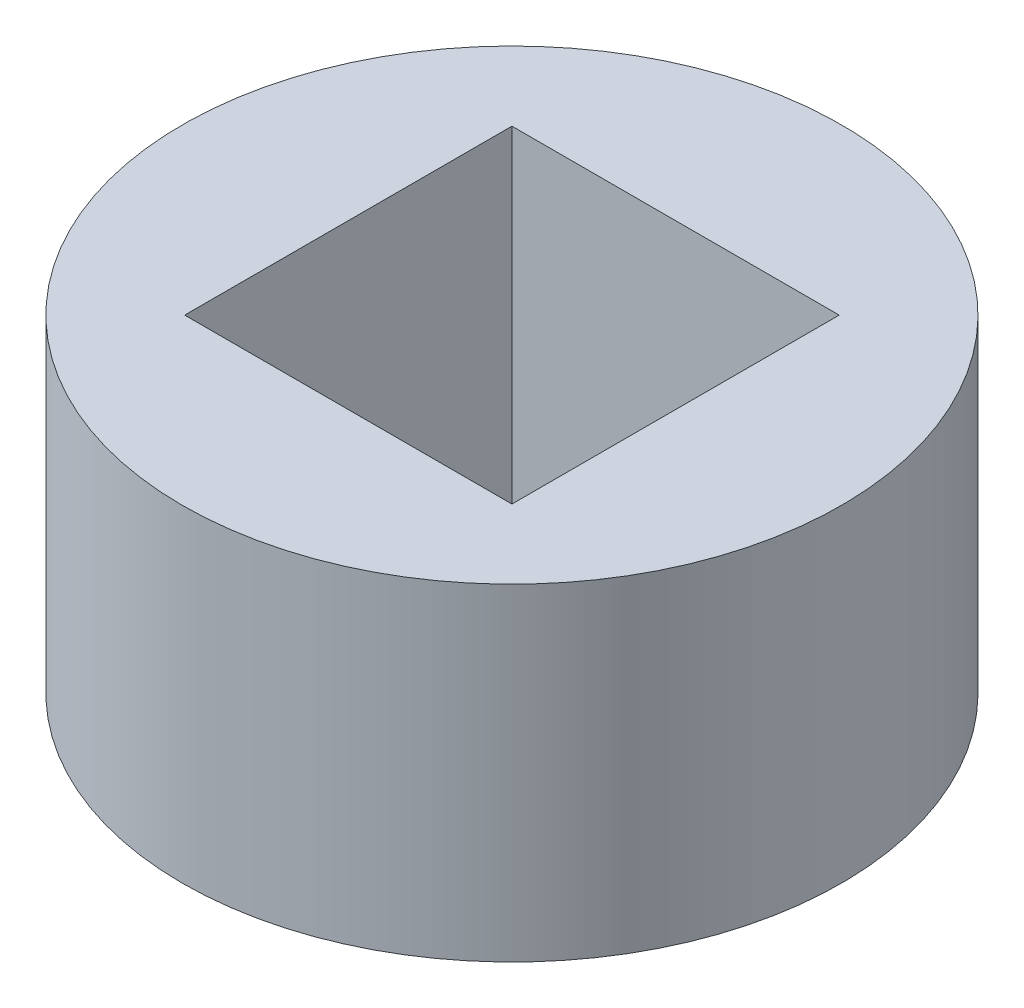
SolidWorks part; units mm, degrees
ref_plane "Front Plane" through (0, 0, 0) normal (0, 0, 1) x (1, 0, 0)
ref_plane "Top Plane" through (0, 0, 0) normal (0, 1, 0) x (1, 0, 0)
ref_plane "Right Plane" through (0, 0, 0) normal (1, 0, 0) x (0, 0, -1)
sketch "Elevator Axle Bearing" plane through (0, 0, 0) normal (0, 1, 0) x (1, 0, 0)
  line L1 (-3.175, 3.175) -> (3.175, 3.175)
  line L2 (-3.175, 3.175) -> (-3.175, -3.175)
  line L3 (-3.175, -3.175) -> (3.175, -3.175)
  line L4 (3.175, 3.175) -> (3.175, -3.175)
  line L5 (-3.175, 3.175) -> (3.175, -3.175) construction
  line L6 (-3.175, -3.175) -> (3.175, 3.175) construction
  circle A0 centre (0, 0) radius 6.3951
  dimension "D1" = 12.7903
  dimension "D2" = 6.35
  dimension "D3" = 6.35
extrude "Boss-Extrude1" add sketch "Elevator Axle Bearing" along normal blind 6.35
equation "\"Ball Diameter\"= 1.75in"
equation "\"Sheet Thickness\"= 0.25in"
equation "\"Screw Diameter\"= .17in"
equation "\"Robot Diameter\"= 14in"
equation "\"Castor Screw Diameter\"= 0.22in"
equation "\"Wheel Diameter\" = 4in"
equation "\"Nut Diameter\" = 8.4mm"
equation "\"Nut Height\" = 2.9mm"
equation "\"Screw Height\" = 0.55in"
equation "\"Pulley Diameter\" = 1in"
equation "\"Reactor Height\" = 14in"
equation "\"Elevator Height\" = 11.5in"
equation "\"Elevator Width\" = \"Ball Diameter\" + 0.25in"
equation "\"Elevator Bearing Diameter\" = sqr(2*(\"Sheet Thickness\"^2)) + 0.2in"
equation "\"Elevator Axle Length\" = \"Elevator Width\" + 8*\"Sheet Thickness\""
equation "\"D1@Elevator Axle Bearing\"=\"Elevator Bearing Diameter\"- 0.05in"
equation "\"D2@Elevator Axle Bearing\"=\"Sheet Thickness\""
equation "\"D3@Elevator Axle Bearing\"=\"Sheet Thickness\""
equation "\"D1@Boss-Extrude1\"=\"Sheet Thickness\""
